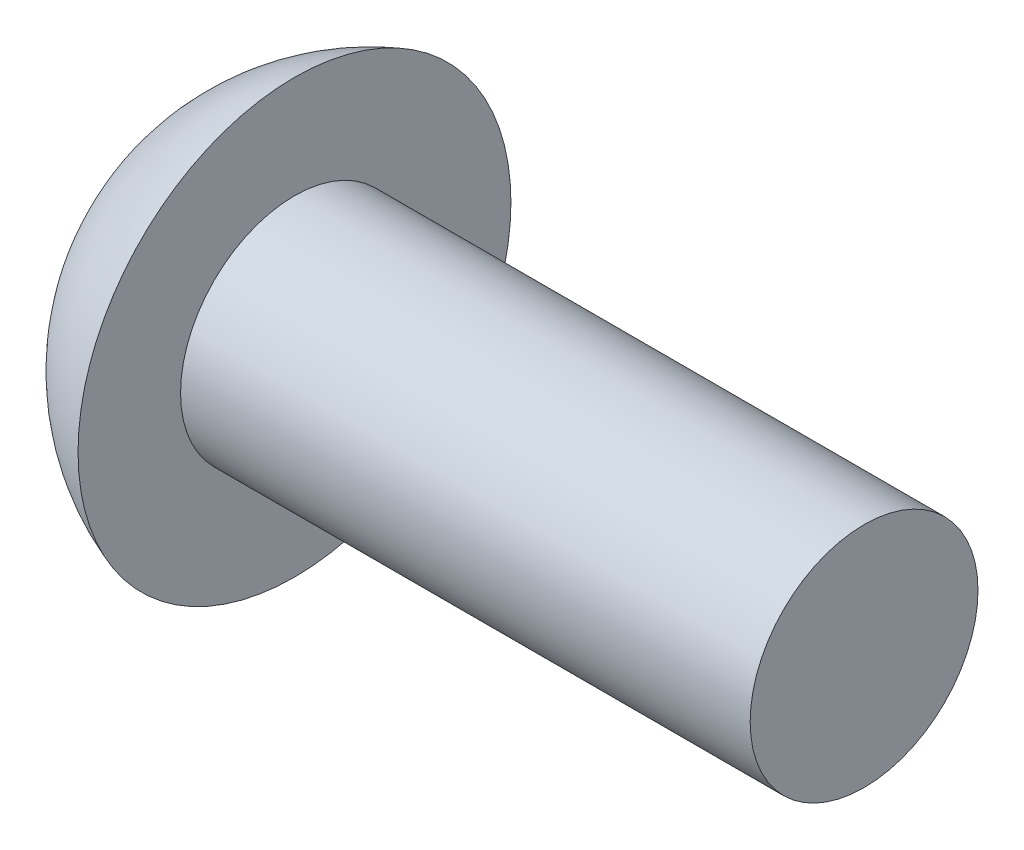
SolidWorks part; units mm, degrees
ref_plane "Front" through (0, 0, 0) normal (0, 0, 1) x (1, 0, 0)
ref_plane "Top" through (0, 0, 0) normal (0, 1, 0) x (1, 0, 0)
ref_plane "Right" through (0, 0, 0) normal (1, 0, 0) x (0, 0, -1)
other "Configuration Table"
sketch "Sketch1" plane through (0, 0, 0) normal (1, 0, 0) x (0, 0, -1)
  line L0 (0, 0) -> (1.4, 0) construction
  circle A0 centre (0, 0) radius 3.8
extrude "BaseHead" add sketch "Sketch1" along normal blind 2.2
sketch "Sketch2" plane through (2.2, 0, 0) normal (1, 0, 0) x (0, 0, -1)
  circle A0 centre (0, 0) radius 2
extrude "BaseBody" add sketch "Sketch2" along normal blind 10
cosmetic thread "ThreadCosmetic1" [suppressed] parameters "D1"=8.6, "THD_MINOR"=3.242
fillet "HeadFillet" [suppressed] radius 0.2
sketch "Sketch3" plane through (-13.4796, 2.4796, 0) normal (0, 0, 1) x (0, -1, 0)
  line L0 (2.4796, 13.4796) -> (2.4796, 41.0387) construction
  line L3 (-1.3204, 13.4796) -> (2.4796, 13.4796) construction
  line L5 (-6.3204, 15.6796) -> (-6.3204, 8.4796)
  line L6 (0.5446, 13.4796) -> (0.5446, 8.4796)
  line L7 (0.5446, 8.4796) -> (-6.3204, 8.4796)
  line L8 (-6.3204, 15.6796) -> (-1.3204, 15.6796)
  line L9 (-1.3204, 13.4796) -> (6.2796, 13.4796) construction
  arc A0 (-1.3204, 15.6796) -> (0.5446, 13.4796) centre (2.4796, 17.0104) ccw
  dimension "D2" = 5
  dimension "e" = 3.87
  dimension "D3" = 5
revolve "Cut-Revolve1" cut sketch "Sketch3" angle 360 about L0
sketch "Sketch4" plane through (0, 0, 0) normal (1, 0, 0) x (0, 0, -1)
  line L1 (1.4434, 0) -> (0.7217, 1.25)
  line L2 (0.7217, 1.25) -> (-0.7217, 1.25)
  line L3 (-0.7217, 1.25) -> (-1.4434, 0)
  line L4 (-1.4434, 0) -> (-0.7217, -1.25)
  line L5 (-0.7217, -1.25) -> (0.7217, -1.25)
  line L6 (0.7217, -1.25) -> (1.4434, 0)
  circle A0 centre (0, 0) radius 1.25 construction
  dimension "s" = 2.5
extrude "HexagonSocket" cut sketch "Sketch4" along normal blind 1.3
sketch "Sketch5" plane through (1.3, 0, 0) normal (-1, 0, 0) x (0, 0, 1)
  line L0 (0.7217, -1.25) -> (-0.7217, -1.25) construction
  line L1 (-0.7217, -1.25) -> (-1.4434, 0) construction
  line L2 (1.4434, 0) -> (0.7217, -1.25) construction
  line L3 (0.7217, 1.25) -> (1.4434, 0) construction
  line L4 (-1.4434, 0) -> (-0.7217, 1.25) construction
  line L5 (-0.7217, 1.25) -> (0.7217, 1.25) construction
  line L6 (0.7217, -1.25) -> (-0.7217, -1.25)
  line L7 (-0.7217, -1.25) -> (-1.4434, 0)
  line L8 (1.4434, 0) -> (0.7217, -1.25)
  line L9 (0.7217, 1.25) -> (1.4434, 0)
  line L10 (-1.4434, 0) -> (-0.7217, 1.25)
  line L11 (-0.7217, 1.25) -> (0.7217, 1.25)
extrude "Cut-Extrude2" cut sketch "Sketch5" against normal blind 5 draft 60
sketch "Sketch6" plane through (0, 0, 0) normal (0, 0, 1) x (1, 0, 0)
  line L0 (12.2, 1.6718) -> (12.3895, 2)
  line L1 (12.3895, 2) -> (12.3895, 2.379)
  line L2 (12.3895, 2.379) -> (12.0105, 2.379)
  line L3 (12.0105, 2.379) -> (12.0105, 2)
  line L4 (12.0105, 2) -> (12.2, 1.6718)
  line L5 (0, 0) -> (24.7294, 0) construction
  line L6 (12.2, -2) -> (12.2, 2) construction
  dimension "D1" = 0.379
  dimension "D2" = 4
revolve "Cut-Revolve10" [suppressed] cut sketch "Sketch6" angle 360 about L5
pattern_linear "LPattern10" [suppressed] count 20 spacing 0.4548 along (-1, 0, 0) of bodies 106
equation "\"D1@ThreadCosmetic1\" = \"l@BaseBody\" - \"a@Sketch1\""
equation "\"D2@Sketch6\" = \"d@Sketch2\""
equation "\"D1@Sketch6\" =  (\"d@Sketch2\" - \"THD_MINOR@ThreadCosmetic1\" )  / 2"
equation "\"D3@LPattern10\" = \"D1@Sketch6\" * 1.2"
equation "\"D1@LPattern10\" = \"D1@ThreadCosmetic1\" / \"D3@LPattern10\" + 1"
